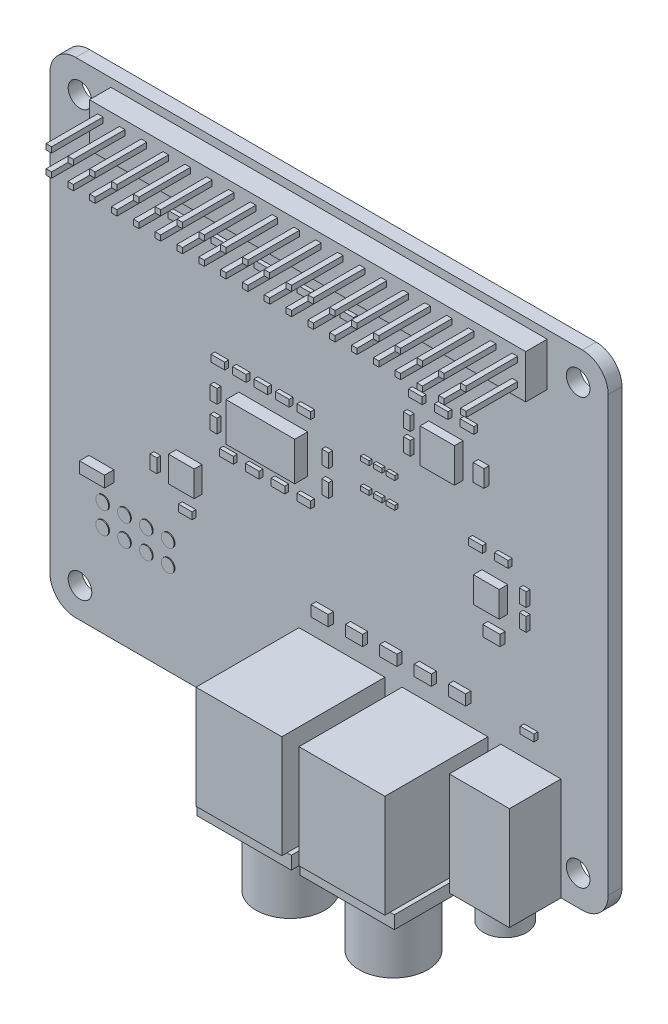
SolidWorks part; units mm, degrees
ref_plane "Front Plane" through (0, 0, 0) normal (0, 0, 1) x (1, 0, 0)
ref_plane "Top Plane" through (0, 0, 0) normal (0, 1, 0) x (1, 0, 0)
ref_plane "Right Plane" through (0, 0, 0) normal (1, 0, 0) x (0, 0, -1)
sketch "Sketch1" plane through (0, 0, 0) normal (0, 0, 1) x (1, 0, 0)
  line L0 (3, 0) -> (62, 0)
  line L1 (65, 3) -> (65, 53.5)
  line L2 (62, 56.5) -> (3, 56.5)
  line L3 (0, 53.5) -> (0, 3)
  arc A0 (62, 0) -> (65, 3) centre (62, 3) ccw
  arc A1 (65, 53.5) -> (62, 56.5) centre (62, 53.5) ccw
  arc A2 (3, 56.5) -> (0, 53.5) centre (3, 53.5) ccw
  arc A3 (0, 3) -> (3, 0) centre (3, 3) ccw
extrude "PCB" add sketch "Sketch1" along normal blind 1.6
ref_plane "Plane_z1_6" through (0, 0, 1.6) normal (0, 0, 1) x (1, 0, 0)
sketch "Sketch2" plane through (0, 0, 1.6) normal (0, 0, 1) x (1, 0, 0)
  line L1 (7.1, 50.46) -> (57.9, 50.46)
  line L2 (7.1, 50.46) -> (7.1, 55.54)
  line L3 (7.1, 55.54) -> (57.9, 55.54)
  line L4 (57.9, 50.46) -> (57.9, 55.54)
extrude "Header_Block" add sketch "Sketch2" along normal blind 2.5
ref_plane "Plane_z4_1" through (0, 0, 4.1) normal (0, 0, 1) x (1, 0, 0)
sketch "Sketch3" plane through (0, 0, 4.1) normal (0, 0, 1) x (1, 0, 0)
  line L1 (8.05, 51.41) -> (8.69, 51.41)
  line L2 (8.05, 51.41) -> (8.05, 52.05)
  line L3 (8.05, 52.05) -> (8.69, 52.05)
  line L4 (8.69, 51.41) -> (8.69, 52.05)
  line L6 (8.05, 53.95) -> (8.69, 53.95)
  line L7 (8.05, 53.95) -> (8.05, 54.59)
  line L8 (8.05, 54.59) -> (8.69, 54.59)
  line L9 (8.69, 53.95) -> (8.69, 54.59)
  line L11 (10.59, 51.41) -> (11.23, 51.41)
  line L12 (10.59, 51.41) -> (10.59, 52.05)
  line L13 (10.59, 52.05) -> (11.23, 52.05)
  line L14 (11.23, 51.41) -> (11.23, 52.05)
  line L16 (10.59, 53.95) -> (11.23, 53.95)
  line L17 (10.59, 53.95) -> (10.59, 54.59)
  line L18 (10.59, 54.59) -> (11.23, 54.59)
  line L19 (11.23, 53.95) -> (11.23, 54.59)
  line L21 (13.13, 51.41) -> (13.77, 51.41)
  line L22 (13.13, 51.41) -> (13.13, 52.05)
  line L23 (13.13, 52.05) -> (13.77, 52.05)
  line L24 (13.77, 51.41) -> (13.77, 52.05)
  line L26 (13.13, 53.95) -> (13.77, 53.95)
  line L27 (13.13, 53.95) -> (13.13, 54.59)
  line L28 (13.13, 54.59) -> (13.77, 54.59)
  line L29 (13.77, 53.95) -> (13.77, 54.59)
  line L31 (15.67, 51.41) -> (16.31, 51.41)
  line L32 (15.67, 51.41) -> (15.67, 52.05)
  line L33 (15.67, 52.05) -> (16.31, 52.05)
  line L34 (16.31, 51.41) -> (16.31, 52.05)
  line L36 (15.67, 53.95) -> (16.31, 53.95)
  line L37 (15.67, 53.95) -> (15.67, 54.59)
  line L38 (15.67, 54.59) -> (16.31, 54.59)
  line L39 (16.31, 53.95) -> (16.31, 54.59)
  line L41 (18.21, 51.41) -> (18.85, 51.41)
  line L42 (18.21, 51.41) -> (18.21, 52.05)
  line L43 (18.21, 52.05) -> (18.85, 52.05)
  line L44 (18.85, 51.41) -> (18.85, 52.05)
  line L46 (18.21, 53.95) -> (18.85, 53.95)
  line L47 (18.21, 53.95) -> (18.21, 54.59)
  line L48 (18.21, 54.59) -> (18.85, 54.59)
  line L49 (18.85, 53.95) -> (18.85, 54.59)
  line L51 (20.75, 51.41) -> (21.39, 51.41)
  line L52 (20.75, 51.41) -> (20.75, 52.05)
  line L53 (20.75, 52.05) -> (21.39, 52.05)
  line L54 (21.39, 51.41) -> (21.39, 52.05)
  line L56 (20.75, 53.95) -> (21.39, 53.95)
  line L57 (20.75, 53.95) -> (20.75, 54.59)
  line L58 (20.75, 54.59) -> (21.39, 54.59)
  line L59 (21.39, 53.95) -> (21.39, 54.59)
  line L61 (23.29, 51.41) -> (23.93, 51.41)
  line L62 (23.29, 51.41) -> (23.29, 52.05)
  line L63 (23.29, 52.05) -> (23.93, 52.05)
  line L64 (23.93, 51.41) -> (23.93, 52.05)
  line L66 (23.29, 53.95) -> (23.93, 53.95)
  line L67 (23.29, 53.95) -> (23.29, 54.59)
  line L68 (23.29, 54.59) -> (23.93, 54.59)
  line L69 (23.93, 53.95) -> (23.93, 54.59)
  line L71 (25.83, 51.41) -> (26.47, 51.41)
  line L72 (25.83, 51.41) -> (25.83, 52.05)
  line L73 (25.83, 52.05) -> (26.47, 52.05)
  line L74 (26.47, 51.41) -> (26.47, 52.05)
  line L76 (25.83, 53.95) -> (26.47, 53.95)
  line L77 (25.83, 53.95) -> (25.83, 54.59)
  line L78 (25.83, 54.59) -> (26.47, 54.59)
  line L79 (26.47, 53.95) -> (26.47, 54.59)
  line L81 (28.37, 51.41) -> (29.01, 51.41)
  line L82 (28.37, 51.41) -> (28.37, 52.05)
  line L83 (28.37, 52.05) -> (29.01, 52.05)
  line L84 (29.01, 51.41) -> (29.01, 52.05)
  line L86 (28.37, 53.95) -> (29.01, 53.95)
  line L87 (28.37, 53.95) -> (28.37, 54.59)
  line L88 (28.37, 54.59) -> (29.01, 54.59)
  line L89 (29.01, 53.95) -> (29.01, 54.59)
  line L91 (30.91, 51.41) -> (31.55, 51.41)
  line L92 (30.91, 51.41) -> (30.91, 52.05)
  line L93 (30.91, 52.05) -> (31.55, 52.05)
  line L94 (31.55, 51.41) -> (31.55, 52.05)
  line L96 (30.91, 53.95) -> (31.55, 53.95)
  line L97 (30.91, 53.95) -> (30.91, 54.59)
  line L98 (30.91, 54.59) -> (31.55, 54.59)
  line L99 (31.55, 53.95) -> (31.55, 54.59)
  line L101 (33.45, 51.41) -> (34.09, 51.41)
  line L102 (33.45, 51.41) -> (33.45, 52.05)
  line L103 (33.45, 52.05) -> (34.09, 52.05)
  line L104 (34.09, 51.41) -> (34.09, 52.05)
  line L106 (33.45, 53.95) -> (34.09, 53.95)
  line L107 (33.45, 53.95) -> (33.45, 54.59)
  line L108 (33.45, 54.59) -> (34.09, 54.59)
  line L109 (34.09, 53.95) -> (34.09, 54.59)
  line L111 (35.99, 51.41) -> (36.63, 51.41)
  line L112 (35.99, 51.41) -> (35.99, 52.05)
  line L113 (35.99, 52.05) -> (36.63, 52.05)
  line L114 (36.63, 51.41) -> (36.63, 52.05)
  line L116 (35.99, 53.95) -> (36.63, 53.95)
  line L117 (35.99, 53.95) -> (35.99, 54.59)
  line L118 (35.99, 54.59) -> (36.63, 54.59)
  line L119 (36.63, 53.95) -> (36.63, 54.59)
  line L121 (38.53, 51.41) -> (39.17, 51.41)
  line L122 (38.53, 51.41) -> (38.53, 52.05)
  line L123 (38.53, 52.05) -> (39.17, 52.05)
  line L124 (39.17, 51.41) -> (39.17, 52.05)
  line L126 (38.53, 53.95) -> (39.17, 53.95)
  line L127 (38.53, 53.95) -> (38.53, 54.59)
  line L128 (38.53, 54.59) -> (39.17, 54.59)
  line L129 (39.17, 53.95) -> (39.17, 54.59)
  line L131 (41.07, 51.41) -> (41.71, 51.41)
  line L132 (41.07, 51.41) -> (41.07, 52.05)
  line L133 (41.07, 52.05) -> (41.71, 52.05)
  line L134 (41.71, 51.41) -> (41.71, 52.05)
  line L136 (41.07, 53.95) -> (41.71, 53.95)
  line L137 (41.07, 53.95) -> (41.07, 54.59)
  line L138 (41.07, 54.59) -> (41.71, 54.59)
  line L139 (41.71, 53.95) -> (41.71, 54.59)
  line L141 (43.61, 51.41) -> (44.25, 51.41)
  line L142 (43.61, 51.41) -> (43.61, 52.05)
  line L143 (43.61, 52.05) -> (44.25, 52.05)
  line L144 (44.25, 51.41) -> (44.25, 52.05)
  line L146 (43.61, 53.95) -> (44.25, 53.95)
  line L147 (43.61, 53.95) -> (43.61, 54.59)
  line L148 (43.61, 54.59) -> (44.25, 54.59)
  line L149 (44.25, 53.95) -> (44.25, 54.59)
  line L151 (46.15, 51.41) -> (46.79, 51.41)
  line L152 (46.15, 51.41) -> (46.15, 52.05)
  line L153 (46.15, 52.05) -> (46.79, 52.05)
  line L154 (46.79, 51.41) -> (46.79, 52.05)
  line L156 (46.15, 53.95) -> (46.79, 53.95)
  line L157 (46.15, 53.95) -> (46.15, 54.59)
  line L158 (46.15, 54.59) -> (46.79, 54.59)
  line L159 (46.79, 53.95) -> (46.79, 54.59)
  line L161 (48.69, 51.41) -> (49.33, 51.41)
  line L162 (48.69, 51.41) -> (48.69, 52.05)
  line L163 (48.69, 52.05) -> (49.33, 52.05)
  line L164 (49.33, 51.41) -> (49.33, 52.05)
  line L166 (48.69, 53.95) -> (49.33, 53.95)
  line L167 (48.69, 53.95) -> (48.69, 54.59)
  line L168 (48.69, 54.59) -> (49.33, 54.59)
  line L169 (49.33, 53.95) -> (49.33, 54.59)
  line L171 (51.23, 51.41) -> (51.87, 51.41)
  line L172 (51.23, 51.41) -> (51.23, 52.05)
  line L173 (51.23, 52.05) -> (51.87, 52.05)
  line L174 (51.87, 51.41) -> (51.87, 52.05)
  line L176 (51.23, 53.95) -> (51.87, 53.95)
  line L177 (51.23, 53.95) -> (51.23, 54.59)
  line L178 (51.23, 54.59) -> (51.87, 54.59)
  line L179 (51.87, 53.95) -> (51.87, 54.59)
  line L181 (53.77, 51.41) -> (54.41, 51.41)
  line L182 (53.77, 51.41) -> (53.77, 52.05)
  line L183 (53.77, 52.05) -> (54.41, 52.05)
  line L184 (54.41, 51.41) -> (54.41, 52.05)
  line L186 (53.77, 53.95) -> (54.41, 53.95)
  line L187 (53.77, 53.95) -> (53.77, 54.59)
  line L188 (53.77, 54.59) -> (54.41, 54.59)
  line L189 (54.41, 53.95) -> (54.41, 54.59)
  line L191 (56.31, 51.41) -> (56.95, 51.41)
  line L192 (56.31, 51.41) -> (56.31, 52.05)
  line L193 (56.31, 52.05) -> (56.95, 52.05)
  line L194 (56.95, 51.41) -> (56.95, 52.05)
  line L196 (56.31, 53.95) -> (56.95, 53.95)
  line L197 (56.31, 53.95) -> (56.31, 54.59)
  line L198 (56.31, 54.59) -> (56.95, 54.59)
  line L199 (56.95, 53.95) -> (56.95, 54.59)
extrude "Header_Pins" add sketch "Sketch3" along normal blind 6
sketch "Sketch4" plane through (0, 0, 1.6) normal (0, 0, 1) x (1, 0, 0)
  line L1 (22, 27.75) -> (30, 27.75)
  line L2 (22, 27.75) -> (22, 32.25)
  line L3 (22, 32.25) -> (30, 32.25)
  line L4 (30, 27.75) -> (30, 32.25)
extrude "IC_DAC" add sketch "Sketch4" along normal blind 1.5
sketch "Sketch5" plane through (0, 0, 1.6) normal (0, 0, 1) x (1, 0, 0)
  line L1 (36.5, 29.75) -> (37.5, 29.75)
  line L2 (36.5, 29.75) -> (36.5, 30.25)
  line L3 (36.5, 30.25) -> (37.5, 30.25)
  line L4 (37.5, 29.75) -> (37.5, 30.25)
  line L6 (38, 29.75) -> (39, 29.75)
  line L7 (38, 29.75) -> (38, 30.25)
  line L8 (38, 30.25) -> (39, 30.25)
  line L9 (39, 29.75) -> (39, 30.25)
  line L11 (39.5, 29.75) -> (40.5, 29.75)
  line L12 (39.5, 29.75) -> (39.5, 30.25)
  line L13 (39.5, 30.25) -> (40.5, 30.25)
  line L14 (40.5, 29.75) -> (40.5, 30.25)
  line L16 (36.5, 32.75) -> (37.5, 32.75)
  line L17 (36.5, 32.75) -> (36.5, 33.25)
  line L18 (36.5, 33.25) -> (37.5, 33.25)
  line L19 (37.5, 32.75) -> (37.5, 33.25)
  line L21 (38, 32.75) -> (39, 32.75)
  line L22 (38, 32.75) -> (38, 33.25)
  line L23 (38, 33.25) -> (39, 33.25)
  line L24 (39, 32.75) -> (39, 33.25)
  line L26 (39.5, 32.75) -> (40.5, 32.75)
  line L27 (39.5, 32.75) -> (39.5, 33.25)
  line L28 (39.5, 33.25) -> (40.5, 33.25)
  line L29 (40.5, 32.75) -> (40.5, 33.25)
extrude "SMD_h0_35" add sketch "Sketch5" along normal blind 0.35
sketch "Sketch6" plane through (0, 0, 1.6) normal (0, 0, 1) x (1, 0, 0)
  line L1 (19.2, 34.1) -> (20.8, 34.1)
  line L2 (19.2, 34.1) -> (19.2, 34.9)
  line L3 (19.2, 34.9) -> (20.8, 34.9)
  line L4 (20.8, 34.1) -> (20.8, 34.9)
  line L6 (21.7, 34.1) -> (23.3, 34.1)
  line L7 (21.7, 34.1) -> (21.7, 34.9)
  line L8 (21.7, 34.9) -> (23.3, 34.9)
  line L9 (23.3, 34.1) -> (23.3, 34.9)
  line L11 (24.2, 34.1) -> (25.8, 34.1)
  line L12 (24.2, 34.1) -> (24.2, 34.9)
  line L13 (24.2, 34.9) -> (25.8, 34.9)
  line L14 (25.8, 34.1) -> (25.8, 34.9)
  line L16 (26.7, 34.1) -> (28.3, 34.1)
  line L17 (26.7, 34.1) -> (26.7, 34.9)
  line L18 (26.7, 34.9) -> (28.3, 34.9)
  line L19 (28.3, 34.1) -> (28.3, 34.9)
  line L21 (29.2, 34.1) -> (30.8, 34.1)
  line L22 (29.2, 34.1) -> (29.2, 34.9)
  line L23 (29.2, 34.9) -> (30.8, 34.9)
  line L24 (30.8, 34.1) -> (30.8, 34.9)
  line L26 (20.2, 25.1) -> (21.8, 25.1)
  line L27 (20.2, 25.1) -> (20.2, 25.9)
  line L28 (20.2, 25.9) -> (21.8, 25.9)
  line L29 (21.8, 25.1) -> (21.8, 25.9)
  line L31 (23.2, 25.1) -> (24.8, 25.1)
  line L32 (23.2, 25.1) -> (23.2, 25.9)
  line L33 (23.2, 25.9) -> (24.8, 25.9)
  line L34 (24.8, 25.1) -> (24.8, 25.9)
  line L36 (26.2, 25.1) -> (27.8, 25.1)
  line L37 (26.2, 25.1) -> (26.2, 25.9)
  line L38 (26.2, 25.9) -> (27.8, 25.9)
  line L39 (27.8, 25.1) -> (27.8, 25.9)
  line L41 (29.2, 25.1) -> (30.8, 25.1)
  line L42 (29.2, 25.1) -> (29.2, 25.9)
  line L43 (29.2, 25.9) -> (30.8, 25.9)
  line L44 (30.8, 25.1) -> (30.8, 25.9)
  line L46 (19.1, 27.2) -> (19.9, 27.2)
  line L47 (19.1, 27.2) -> (19.1, 28.8)
  line L48 (19.1, 28.8) -> (19.9, 28.8)
  line L49 (19.9, 27.2) -> (19.9, 28.8)
  line L51 (19.1, 30.2) -> (19.9, 30.2)
  line L52 (19.1, 30.2) -> (19.1, 31.8)
  line L53 (19.1, 31.8) -> (19.9, 31.8)
  line L54 (19.9, 30.2) -> (19.9, 31.8)
  line L56 (32.1, 27.2) -> (32.9, 27.2)
  line L57 (32.1, 27.2) -> (32.1, 28.8)
  line L58 (32.1, 28.8) -> (32.9, 28.8)
  line L59 (32.9, 27.2) -> (32.9, 28.8)
  line L61 (32.1, 30.2) -> (32.9, 30.2)
  line L62 (32.1, 30.2) -> (32.1, 31.8)
  line L63 (32.1, 31.8) -> (32.9, 31.8)
  line L64 (32.9, 30.2) -> (32.9, 31.8)
  line L66 (42.2, 42.1) -> (43.8, 42.1)
  line L67 (42.2, 42.1) -> (42.2, 42.9)
  line L68 (42.2, 42.9) -> (43.8, 42.9)
  line L69 (43.8, 42.1) -> (43.8, 42.9)
  line L71 (45.2, 42.1) -> (46.8, 42.1)
  line L72 (45.2, 42.1) -> (45.2, 42.9)
  line L73 (45.2, 42.9) -> (46.8, 42.9)
  line L74 (46.8, 42.1) -> (46.8, 42.9)
  line L76 (48.2, 42.1) -> (49.8, 42.1)
  line L77 (48.2, 42.1) -> (48.2, 42.9)
  line L78 (48.2, 42.9) -> (49.8, 42.9)
  line L79 (49.8, 42.1) -> (49.8, 42.9)
  line L81 (41.6, 36.2) -> (42.4, 36.2)
  line L82 (41.6, 36.2) -> (41.6, 37.8)
  line L83 (41.6, 37.8) -> (42.4, 37.8)
  line L84 (42.4, 36.2) -> (42.4, 37.8)
  line L86 (41.6, 38.7) -> (42.4, 38.7)
  line L87 (41.6, 38.7) -> (41.6, 40.3)
  line L88 (41.6, 40.3) -> (42.4, 40.3)
  line L89 (42.4, 38.7) -> (42.4, 40.3)
  line L91 (55.1, 25.2) -> (55.9, 25.2)
  line L92 (55.1, 25.2) -> (55.1, 26.8)
  line L93 (55.1, 26.8) -> (55.9, 26.8)
  line L94 (55.9, 25.2) -> (55.9, 26.8)
  line L96 (55.1, 27.7) -> (55.9, 27.7)
  line L97 (55.1, 27.7) -> (55.1, 29.3)
  line L98 (55.1, 29.3) -> (55.9, 29.3)
  line L99 (55.9, 27.7) -> (55.9, 29.3)
  line L101 (49.2, 30.6) -> (50.8, 30.6)
  line L102 (49.2, 30.6) -> (49.2, 31.4)
  line L103 (49.2, 31.4) -> (50.8, 31.4)
  line L104 (50.8, 30.6) -> (50.8, 31.4)
  line L106 (52.2, 30.6) -> (53.8, 30.6)
  line L107 (52.2, 30.6) -> (52.2, 31.4)
  line L108 (52.2, 31.4) -> (53.8, 31.4)
  line L109 (53.8, 30.6) -> (53.8, 31.4)
  line L111 (55.2, 14.6) -> (56.8, 14.6)
  line L112 (55.2, 14.6) -> (55.2, 15.4)
  line L113 (55.2, 15.4) -> (56.8, 15.4)
  line L114 (56.8, 14.6) -> (56.8, 15.4)
  line L116 (14.2, 46.1) -> (15.8, 46.1)
  line L117 (14.2, 46.1) -> (14.2, 46.9)
  line L118 (14.2, 46.9) -> (15.8, 46.9)
  line L119 (15.8, 46.1) -> (15.8, 46.9)
  line L121 (19.2, 46.1) -> (20.8, 46.1)
  line L122 (19.2, 46.1) -> (19.2, 46.9)
  line L123 (19.2, 46.9) -> (20.8, 46.9)
  line L124 (20.8, 46.1) -> (20.8, 46.9)
  line L126 (24.2, 46.1) -> (25.8, 46.1)
  line L127 (24.2, 46.1) -> (24.2, 46.9)
  line L128 (24.2, 46.9) -> (25.8, 46.9)
  line L129 (25.8, 46.1) -> (25.8, 46.9)
  line L131 (29.2, 46.1) -> (30.8, 46.1)
  line L132 (29.2, 46.1) -> (29.2, 46.9)
  line L133 (29.2, 46.9) -> (30.8, 46.9)
  line L134 (30.8, 46.1) -> (30.8, 46.9)
  line L136 (34.2, 46.1) -> (35.8, 46.1)
  line L137 (34.2, 46.1) -> (34.2, 46.9)
  line L138 (34.2, 46.9) -> (35.8, 46.9)
  line L139 (35.8, 46.1) -> (35.8, 46.9)
  line L141 (12.1, 19.7) -> (12.9, 19.7)
  line L142 (12.1, 19.7) -> (12.1, 21.3)
  line L143 (12.1, 21.3) -> (12.9, 21.3)
  line L144 (12.9, 19.7) -> (12.9, 21.3)
  line L146 (15.4, 17.1) -> (17, 17.1)
  line L147 (15.4, 17.1) -> (15.4, 17.9)
  line L148 (15.4, 17.9) -> (17, 17.9)
  line L149 (17, 17.1) -> (17, 17.9)
extrude "SMD_h0_45" add sketch "Sketch6" along normal blind 0.45
sketch "Sketch7" plane through (0, 0, 1.6) normal (0, 0, 1) x (1, 0, 0)
  line L1 (49.875, 37.4) -> (51.125, 37.4)
  line L2 (49.875, 37.4) -> (49.875, 39.4)
  line L3 (49.875, 39.4) -> (51.125, 39.4)
  line L4 (51.125, 37.4) -> (51.125, 39.4)
  line L6 (51, 22.375) -> (53, 22.375)
  line L7 (51, 22.375) -> (51, 23.625)
  line L8 (51, 23.625) -> (53, 23.625)
  line L9 (53, 22.375) -> (53, 23.625)
  line L11 (31, 14.375) -> (33, 14.375)
  line L12 (31, 14.375) -> (31, 15.625)
  line L13 (31, 15.625) -> (33, 15.625)
  line L14 (33, 14.375) -> (33, 15.625)
  line L16 (35, 14.375) -> (37, 14.375)
  line L17 (35, 14.375) -> (35, 15.625)
  line L18 (35, 15.625) -> (37, 15.625)
  line L19 (37, 14.375) -> (37, 15.625)
  line L21 (39, 14.375) -> (41, 14.375)
  line L22 (39, 14.375) -> (39, 15.625)
  line L23 (39, 15.625) -> (41, 15.625)
  line L24 (41, 14.375) -> (41, 15.625)
  line L26 (43, 14.375) -> (45, 14.375)
  line L27 (43, 14.375) -> (43, 15.625)
  line L28 (43, 15.625) -> (45, 15.625)
  line L29 (45, 14.375) -> (45, 15.625)
  line L31 (47, 14.375) -> (49, 14.375)
  line L32 (47, 14.375) -> (47, 15.625)
  line L33 (47, 15.625) -> (49, 15.625)
  line L34 (49, 14.375) -> (49, 15.625)
extrude "SMD_h0_6" add sketch "Sketch7" along normal blind 0.6
sketch "Sketch8" plane through (0, 0, 1.6) normal (0, 0, 1) x (1, 0, 0)
  line L1 (14.7, 19.8) -> (17.7, 19.8)
  line L2 (14.7, 19.8) -> (14.7, 22.8)
  line L3 (14.7, 22.8) -> (17.7, 22.8)
  line L4 (17.7, 19.8) -> (17.7, 22.8)
extrude "SMD_h0_9" add sketch "Sketch8" along normal blind 0.9
sketch "Sketch9" plane through (0, 0, 1.6) normal (0, 0, 1) x (1, 0, 0)
  line L1 (44.1, 36.4) -> (48.1, 36.4)
  line L2 (44.1, 36.4) -> (44.1, 40.4)
  line L3 (44.1, 40.4) -> (48.1, 40.4)
  line L4 (48.1, 36.4) -> (48.1, 40.4)
  line L6 (50.3, 25.5) -> (53.3, 25.5)
  line L7 (50.3, 25.5) -> (50.3, 28.5)
  line L8 (50.3, 28.5) -> (53.3, 28.5)
  line L9 (53.3, 25.5) -> (53.3, 28.5)
extrude "SMD_h1" add sketch "Sketch9" along normal blind 1
sketch "Sketch10" plane through (0, 0, 1.6) normal (0, 0, 1) x (1, 0, 0)
  line L1 (4.55, 15.85) -> (7.45, 15.85)
  line L2 (4.55, 15.85) -> (4.55, 17.15)
  line L3 (4.55, 17.15) -> (7.45, 17.15)
  line L4 (7.45, 15.85) -> (7.45, 17.15)
extrude "SMD_h1_1" add sketch "Sketch10" along normal blind 1.1
sketch "Sketch11" plane through (0, 0, 1.6) normal (0, 0, 1) x (1, 0, 0)
  circle A0 centre (6.19, 10.73) radius 0.75
  circle A1 centre (6.19, 13.27) radius 0.75
  circle A2 centre (8.73, 10.73) radius 0.75
  circle A3 centre (8.73, 13.27) radius 0.75
  circle A4 centre (11.27, 10.73) radius 0.75
  circle A5 centre (11.27, 13.27) radius 0.75
  circle A6 centre (13.81, 10.73) radius 0.75
  circle A7 centre (13.81, 13.27) radius 0.75
extrude "Test_Pads" add sketch "Sketch11" along normal blind 0.1
sketch "Sketch12" plane through (0, 0, 1.6) normal (0, 0, 1) x (1, 0, 0)
  line L1 (29, 0) -> (39, 0)
  line L2 (29, 0) -> (29, 12)
  line L3 (29, 12) -> (39, 12)
  line L4 (39, 0) -> (39, 12)
  line L6 (41, 0) -> (51, 0)
  line L7 (41, 0) -> (41, 12)
  line L8 (41, 12) -> (51, 12)
  line L9 (51, 0) -> (51, 12)
extrude "RCA_Housings" add sketch "Sketch12" along normal blind 12
sketch "Sketch13" plane through (0, 0, 0) normal (0, 1, 0) x (1, 0, 0)
  line L1 (28.5, -1) -> (39.5, -1)
  line L2 (28.5, -1) -> (28.5, -13)
  line L3 (28.5, -13) -> (39.5, -13)
  line L4 (39.5, -1) -> (39.5, -13)
  line L6 (40.5, -1) -> (51.5, -1)
  line L7 (40.5, -1) -> (40.5, -13)
  line L8 (40.5, -13) -> (51.5, -13)
  line L9 (51.5, -1) -> (51.5, -13)
extrude "RCA_Flanges" add sketch "Sketch13" against normal blind 1.5
sketch "Sketch14" plane through (0, 0, 0) normal (0, 1, 0) x (1, 0, 0)
  circle A0 centre (34, -7.6) radius 4
  circle A1 centre (46, -7.6) radius 4
extrude "RCA_Barrels" add sketch "Sketch14" against normal blind 9
sketch "Sketch15" plane through (0, 0, 1.6) normal (0, 0, 1) x (1, 0, 0)
  line L1 (52.5, 0) -> (59.5, 0)
  line L2 (52.5, 0) -> (52.5, 12)
  line L3 (52.5, 12) -> (59.5, 12)
  line L4 (59.5, 0) -> (59.5, 12)
extrude "Jack_Body" add sketch "Sketch15" along normal blind 6
sketch "Sketch16" plane through (0, 0, 0) normal (0, 1, 0) x (1, 0, 0)
  circle A0 centre (56, -4.6) radius 2.5
extrude "Jack_Nose" add sketch "Sketch16" against normal blind 2.5
sketch "Sketch17" plane through (0, 0, 0) normal (0, 1, 0) x (1, 0, 0)
  circle A0 centre (34, -7.6) radius 2.5
  circle A1 centre (46, -7.6) radius 2.5
extrude "RCA_Bores" cut sketch "Sketch17" along normal blind 9
sketch "Sketch18" plane through (0, 0, 0) normal (0, 1, 0) x (1, 0, 0)
  circle A0 centre (56, -4.6) radius 1.75
extrude "Jack_Bore" cut sketch "Sketch18" along normal blind 2.5
sketch "Sketch19" plane through (0, 0, 0) normal (0, 0, 1) x (1, 0, 0)
  circle A0 centre (3.5, 3.5) radius 1.375
  circle A1 centre (3.5, 53) radius 1.375
  circle A2 centre (61.5, 3.5) radius 1.375
  circle A3 centre (61.5, 53) radius 1.375
extrude "Mount_Holes" cut sketch "Sketch19" against normal through all and the other way through all
equation "\"pcb_l\" = 65mm"
equation "\"pcb_w\" = 56.5mm"
equation "\"pcb_t\" = 1.6mm"
equation "\"pcb_r\" = 3mm"
equation "\"hole_d\" = 2.75mm"
equation "\"hole_inset\" = 3.5mm"
equation "\"hdr_pitch\" = 2.54mm"
equation "\"hdr_block_h\" = 2.5mm"
equation "\"hdr_pin\" = 0.64mm"
equation "\"hdr_pin_h\" = 6mm"
equation "\"rca_x1\" = 34mm"
equation "\"rca_x2\" = 46mm"
equation "\"rca_w\" = 10mm"
equation "\"rca_d\" = 12mm"
equation "\"rca_h\" = 12mm"
equation "\"rca_flange_w\" = 11mm"
equation "\"rca_flange_t\" = 1.5mm"
equation "\"rca_barrel_d\" = 8mm"
equation "\"rca_barrel_out\" = 9mm"
equation "\"rca_bore_d\" = 5mm"
equation "\"jack_x\" = 56mm"
equation "\"jack_w\" = 7mm"
equation "\"jack_d\" = 12mm"
equation "\"jack_h\" = 6mm"
equation "\"jack_nose_d\" = 5mm"
equation "\"jack_nose_out\" = 2.5mm"
equation "\"jack_bore_d\" = 3.5mm"
equation "\"D1@PCB\" = \"pcb_t\""
equation "\"D1@RCA_Barrels\" = \"rca_barrel_out\""
